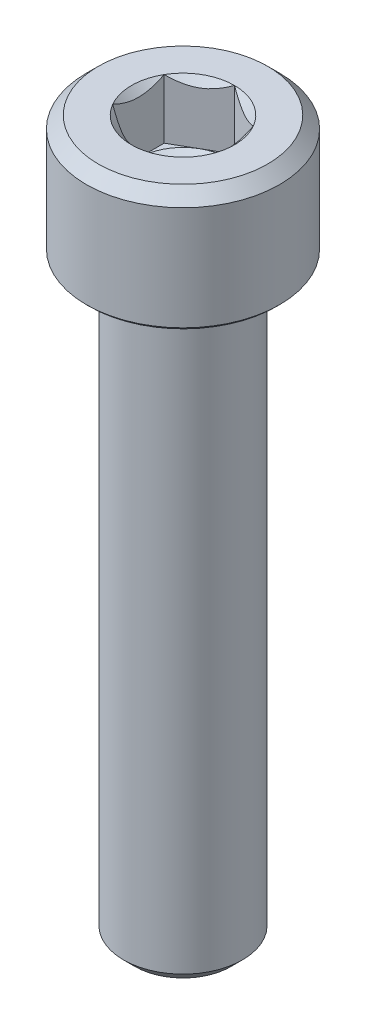
SolidWorks part; units mm, degrees
ref_plane "Front Plane" through (0, 0, 0) normal (0, 0, 1) x (1, 0, 0)
ref_plane "Top Plane" through (0, 0, 0) normal (0, 1, 0) x (1, 0, 0)
ref_plane "Right Plane" through (0, 0, 0) normal (1, 0, 0) x (0, 0, -1)
sketch "Sketch1" plane through (0, 0, 0) normal (0, 0, 1) x (1, 0, 0)
  line L0 (0, 2.2679) -> (3, 4)
  line L1 (3, 4) -> (3, 7.5359)
  line L2 (3, 7.5359) -> (3.4641, 8)
  line L3 (3.4641, 8) -> (5.7, 8)
  line L4 (5.7, 8) -> (6.5, 7.2)
  line L5 (6.5, 7.2) -> (6.5, 0.2)
  line L6 (6.5, 0.2) -> (6.3, 0)
  line L7 (6.3, 0) -> (4.05, 0)
  line L8 (4.05, 0) -> (4, -1.02)
  line L9 (4, -1.02) -> (4, -39.233)
  line L10 (4, -39.233) -> (3.233, -40)
  line L11 (3.233, -40) -> (0, -40)
  line L12 (0, -40) -> (0, 2.2679)
  line L13 (0, -40) -> (0, 8) construction
revolve "Revolve1" add sketch "Sketch1" angle 360 about L13 reverse direction yes
cosmetic thread "Cosmetic Thread1" parameters "D1"=28, "D2"=6.466
ref_plane "Plane1" through (0, 8, 0) normal (0, 1, 0) x (1, 0, 0)
sketch "Sketch2" plane through (0, 8, 0) normal (0, 1, 0) x (1, 0, 0)
  line L0 (-3, -1.7321) -> (0, -3.4641)
  line L1 (0, -3.4641) -> (3, -1.7321)
  line L2 (3, -1.7321) -> (3, 1.7321)
  line L3 (3, 1.7321) -> (0, 3.4641)
  line L4 (0, 3.4641) -> (-3, 1.7321)
  line L5 (-3, 1.7321) -> (-3, -1.7321)
extrude "Cut-Extrude1" cut sketch "Sketch2" against normal blind 4
ref_plane "Plane2" through (0, -40, 0) normal (0, 1, 0) x (1, 0, 0)
ref_plane "ANBAU XY" through (0, 0, 0) normal (0, 1, 0) x (1, 0, 0)
ref_plane "ANBAU XZ" through (0, 0, 0) normal (0, 0, 1) x (1, 0, 0)
ref_plane "ANBAU YZ" through (0, 0, 0) normal (1, 0, 0) x (0, 0, -1)
ref_axis "ANBAU X" through (-80.9, 0, 0) along (1, 0, 0)
ref_axis "ANBAU Y" through (0, 0, 50) along (0, 0, -1)
ref_axis "ANBAU Z" through (0, 50, 0) along (0, -1, 0)
sketch3d "ANBAU"
  point P0 (0, 0, 0)
ref_plane "Schraube XY" through (0, 0, 0) normal (0, 1, 0) x (1, 0, 0)
ref_plane "Schraube XZ" through (0, 0, 0) normal (0, 0, 1) x (1, 0, 0)
ref_plane "Schraube YZ" through (0, 0, 0) normal (1, 0, 0) x (0, 0, -1)
ref_axis "Schraube X" through (-80.9, 0, 0) along (1, 0, 0)
ref_axis "Schraube Y" through (0, 0, 50) along (0, 0, -1)
ref_axis "Schraube Z" through (0, 50, 0) along (0, -1, 0)
sketch3d "Schraube"
  point P0 (0, 0, 0)
ref_plane "insert XY" through (0, 0, 0) normal (0, 1, 0) x (1, 0, 0)
ref_plane "insert XZ" through (0, 0, 0) normal (0, 0, 1) x (1, 0, 0)
ref_plane "insert YZ" through (0, 0, 0) normal (1, 0, 0) x (0, 0, -1)
ref_axis "insert X" through (-80.9, 0, 0) along (1, 0, 0)
ref_axis "insert Y" through (0, 0, 50) along (0, 0, -1)
ref_axis "insert Z" through (0, 50, 0) along (0, -1, 0)
sketch3d "insert"
  point P0 (0, 0, 0)
ref_plane "schrauben_punkt XY" through (0, -40, 0) normal (0, 1, 0) x (1, 0, 0)
ref_plane "schrauben_punkt XZ" through (0, 0, 0) normal (0, 0, 1) x (1, 0, 0)
ref_plane "schrauben_punkt YZ" through (0, 0, 0) normal (1, 0, 0) x (0, 0, -1)
ref_axis "schrauben_punkt X" through (-80.9, -40, 0) along (1, 0, 0)
ref_axis "schrauben_punkt Y" through (0, -40, 50) along (0, 0, -1)
ref_axis "schrauben_punkt Z" through (0, 50, 0) along (0, -1, 0)
sketch3d "schrauben_punkt"
  point P0 (0, -40, 0)
other "Freeze***"
